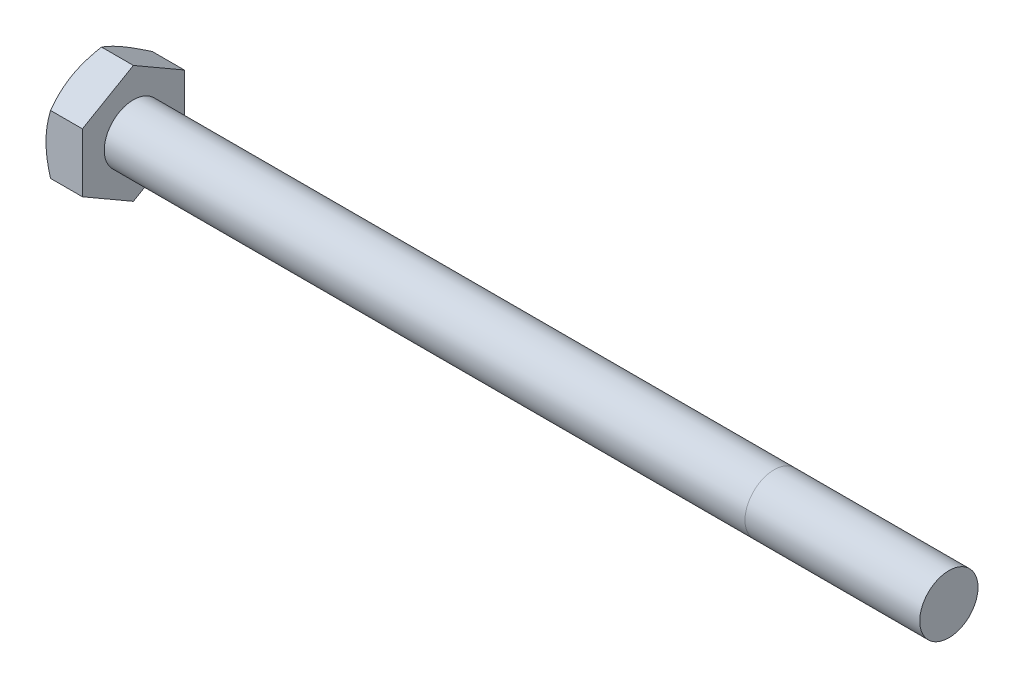
SolidWorks part; units mm, degrees
material "Alloy Steel"
ref_plane "Front Plane" through (0, 0, 0) normal (0, 0, 1) x (1, 0, 0)
ref_plane "Top Plane" through (0, 0, 0) normal (0, 1, 0) x (1, 0, 0)
ref_plane "Right Plane" through (0, 0, 0) normal (1, 0, 0) x (0, 0, -1)
sketch "Sketch1" plane through (0, 0, 0) normal (0, 0, 1) x (1, 0, 0)
  line L0 (-46.4344, 0) -> (46.4344, 0) construction
  line L1 (46.4344, 3.175) -> (46.4344, -3.175) construction
  line L2 (-42.4656, 5.5562) -> (-42.4656, -5.5562) construction
  line L3 (-46.4344, 5.5562) -> (-46.4344, -5.5562) construction
  point P9 (-42.4656, 0)
  point P10 (41.9894, -3.175)
  dimension "D1" = 4.445
  dimension "Screw Dia" = 6.35
  dimension "Hex" = 11.1125
  dimension "Head Ht" = 3.9688
  dimension "Screw Lenght" = 88.9
ref_plane "Plane2" through (46.4344, 0, 0) normal (1, 0, 0) x (0, 0, -1)
sketch "Sketch5" plane through (46.4344, 0, 0) normal (1, 0, 0) x (0, 0, -1)
  circle A0 centre (0, 0) radius 3.175
extrude "Boss-Extrude3" add sketch "Sketch5" against normal up to vertex (88.9 mm away) up to point (-42.4656, 0, 0)
sketch "Sketch9" plane through (46.4344, 0, 0) normal (1, 0, 0) x (0, 0, -1)
  circle A1 centre (0, 0) radius 3.175
  circle A2 centre (0, 0) radius 3.175
  dimension "D1" = 0
curve "Helix/Spiral1" pitch 1.27 height 20.32 turns 16 parameters "Pitch"=1.27
chamfer "Chamfer1" [suppressed] distance 0.9525 angle 45
sketch "Sketch10" plane through (0, 0, 0) normal (0, 0, 1) x (1, 0, 0)
  line L0 (46.4344, 3.175) -> (46.9106, 2.3501)
  line L1 (46.9106, 2.3501) -> (47.0694, 2.3501)
  line L2 (47.0694, 2.3501) -> (47.5456, 3.175)
  line L3 (46.4344, 3.175) -> (47.5456, 3.175)
  line L4 (46.99, 3.175) -> (46.99, 2.3501) construction
  line L5 (46.6725, 2.7626) -> (47.3075, 2.7626) construction
  dimension "D1" = 60
  dimension "D2" = 0.1588
  dimension "D3" = 0.635
sweep "Cut-Sweep1" [suppressed] cut profiles "Sketch10" path "Helix/Spiral1"
sketch "Sketch11" plane through (0, 0, 0) normal (0, 0, 1) x (1, 0, 0)
  line L0 (-42.4656, 3.175) -> (-42.4656, 0)
  line L1 (-42.4656, 0) -> (30.5594, 0)
  line L3 (30.5594, 0) -> (27.3844, 3.175)
  line L4 (-42.4656, 3.175) -> (27.3844, 3.175)
  dimension "D1" = 45
  dimension "MIn Thread" = 19.05
revolve "Revolve1" add sketch "Sketch11" angle 360 about L1
sketch "Sketch6" plane through (-42.4656, 0, 0) normal (-1, 0, 0) x (0, 0, 1)
  line L0 (0, 5.5562) -> (0, -5.5562) construction
  line L1 (5.5563, 3.2079) -> (0, 6.4158)
  line L2 (0, 6.4158) -> (-5.5562, 3.2079)
  line L3 (-5.5562, 3.2079) -> (-5.5562, -3.2079)
  line L4 (-5.5562, -3.2079) -> (0, -6.4158)
  line L5 (0, -6.4158) -> (5.5563, -3.2079)
  line L6 (5.5563, -3.2079) -> (5.5563, 3.2079)
  circle A0 centre (0, 0) radius 5.5563 construction
extrude "Boss-Extrude4" add sketch "Sketch6" along normal up to vertex (3.9688 mm away) up to point (-46.4344, -5.5562, 0)
sketch "Sketch7" plane through (-46.4344, 0, 0) normal (-1, 0, 0) x (0, 0, 1)
  circle A0 centre (0, 0) radius 5.5563 construction
  circle A1 centre (0, 0) radius 5.5563
sketch "Sketch8" plane through (-46.4344, 0, 0) normal (-1, 0, 0) x (0, 0, 1)
  circle A0 centre (0, 0) radius 5.5563 construction
  circle A1 centre (0, 0) radius 5.5563
extrude "Cut-Extrude3" cut sketch "Sketch8" against normal through all draft 60 flip side to cut
sketch "Sketch12" plane through (-46.4344, 0, 0) normal (-1, 0, 0) x (0, 0, 1)
  line L0 (0, 4.2783) -> (0, 2.3892) construction
  line L1 (0.1667, 4.2783) -> (0.1667, 2.3892)
  line L2 (-0.1667, 4.2783) -> (-0.1667, 2.3892)
  line L3 (0, 3.175) -> (0, -3.175) construction
  arc A0 (0.1667, 4.2783) -> (-0.1667, 4.2783) centre (0, 4.2783) ccw
  arc A1 (-0.1667, 2.3892) -> (0.1667, 2.3892) centre (0, 2.3892) ccw
  circle A3 centre (0, 0) radius 2.2225 construction
  circle A4 centre (0, 0) radius 4.445 construction
  point P2 (0, 3.3337)
  dimension "D1" = 4.445
  dimension "D3" = 8.89
  dimension "D2" = 0.3334
extrude "Cut-Extrude4" cut sketch "Sketch12" against normal blind 0.254
pattern_circular "CirPattern1" count 3 over 360 about axis through (-42.4656, 0, 0) along (1, 0, 0) of "Cut-Extrude4"
sketch "Sketch13" plane through (0, 0, 0) normal (0, 1, 0) x (1, 0, 0)
  line L0 (27.3844, -3.175) -> (27.3844, 3.175)
  line L1 (-42.4656, -3.175) -> (46.4344, -3.175) construction
  line L2 (46.4344, 3.175) -> (-42.4656, 3.175) construction
  line L3 (46.4344, -3.175) -> (46.4344, 3.175) construction
  point P8 (27.3844, 0)
  dimension "D1" = 19.05
split line "Split Line4"
equation "\"D2@Sketch10\" = \"Pitch@Helix/Spiral1\"*.125"
equation "\"D3@Sketch10\" = \"Pitch@Helix/Spiral1\"*.5"
equation "\"D3@Helix/Spiral1\" = \"MIn Thread@Sketch11\"+\"Pitch@Helix/Spiral1\""
equation "\"D1@Chamfer1\" = \"Pitch@Helix/Spiral1\"*.75"
equation "\"D1@Sketch12\" = \"Hex@Sketch1\"*.4"
equation "\"D3@Sketch12\" = \"Hex@Sketch1\"*.8"
equation "\"D2@Sketch12\" = \"Hex@Sketch1\"*.03"
equation "\"D1@Sketch1\" = \"Pitch@Helix/Spiral1\"*3.5"
